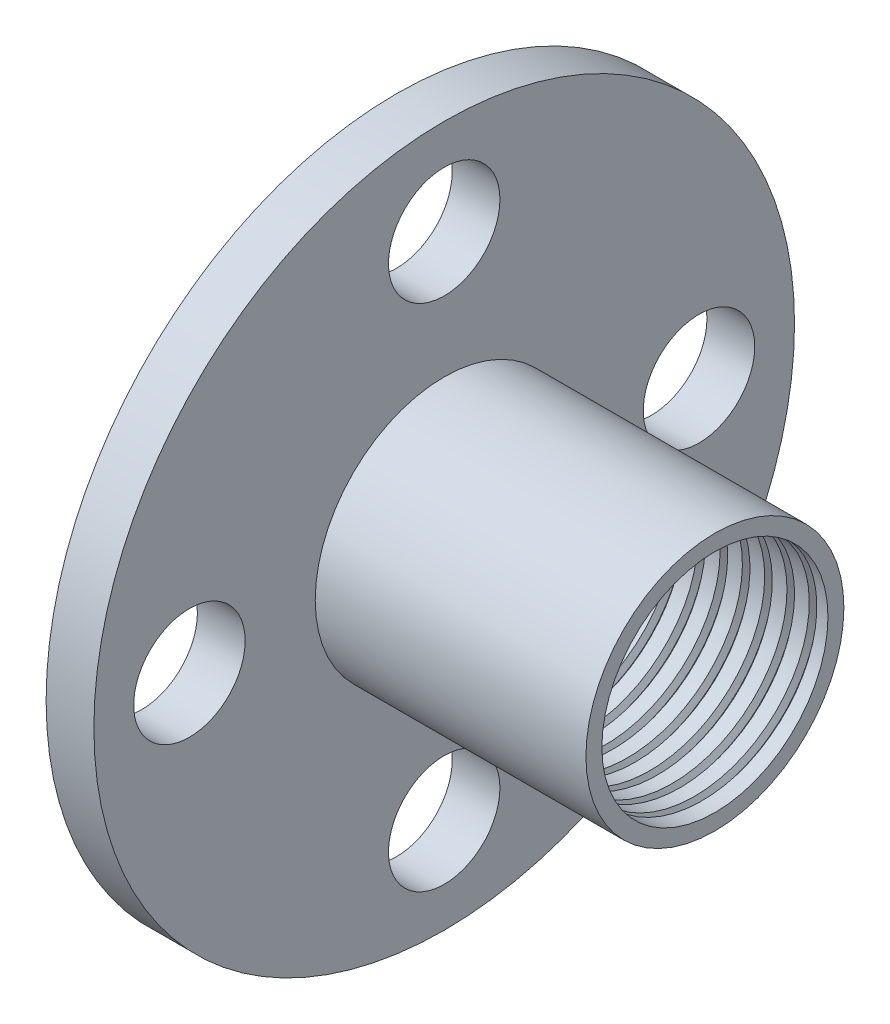
SolidWorks part; units mm, degrees
note: The reader was unsure of these and kept them because the rebuilt part matched: shared geometry of "Sketch1<3>".
ref_plane "Front Plane" through (0, 0, 0) normal (0, 0, 1) x (1, 0, 0)
ref_plane "Top Plane" through (0, 0, 0) normal (0, 1, 0) x (1, 0, 0)
ref_plane "Right Plane" through (0, 0, 0) normal (1, 0, 0) x (0, 0, -1)
sketch "Sketch1" plane through (0, 0, 0) normal (1, 0, 0) x (0, 0, -1)
  line L0 (0, 11) -> (0, 0) construction
  circle A0 centre (0, 0) radius 11
  circle A1 centre (0, 0) radius 4.05
  circle A2 centre (0, 8) radius 1.75
  circle A3 centre (8, 0) radius 1.75
  circle A4 centre (0, -8) radius 1.75
  circle A5 centre (-8, 0) radius 1.75
  point P16 (0, 0)
  dimension "D1" = 8.1
  dimension "D2" = 3.5
  dimension "D4" = 22
  dimension "D3" = 8
  dimension "D5" = 4
extrude "Boss-Extrude1" add sketch "Sketch1" along normal blind 10
extrude "Boss-Extrude2" add sketch "Sketch1<3>" along normal blind 1.5 separate body
sketch "Sketch1<3>" plane through (0, 0, 0) normal (1, 0, 0) x (0, 0, -1) same geometry as "Sketch1"
shell "Shell2" thickness 0.5
thread "Thread1" pitch 0.3175 start angle 0, offset 0, length 0, pitch 0.7, diameter 7.1
ref_plane "Plane1" through (10, 0, 3.55) normal (0, -1, 0) x (0, 0, 1)
sketch "Thread Profile1" plane through (10, 0, 3.55) normal (0, -1, 0) x (0, 0, 1)
  line L0 (0, 0) -> (0, 0.3175) construction
  line L1 (0, 0) -> (0.1719, 0.0992)
  line L2 (0.1719, 0.0992) -> (0.1719, 0.1389)
  line L3 (0.1719, 0.1389) -> (0, 0.2381)
  line L4 (0.1719, 0.1191) -> (0, 0.1191) construction
  line L11 (0, 0) -> (0, 0.2381)
  point P2 (0, 0)
  dimension "Pitch" = 0.3175
  dimension "Profile_Angle" = 60
  dimension "Profile_Land" = 0.0397
  dimension "Profile_Height" = 0.1719
